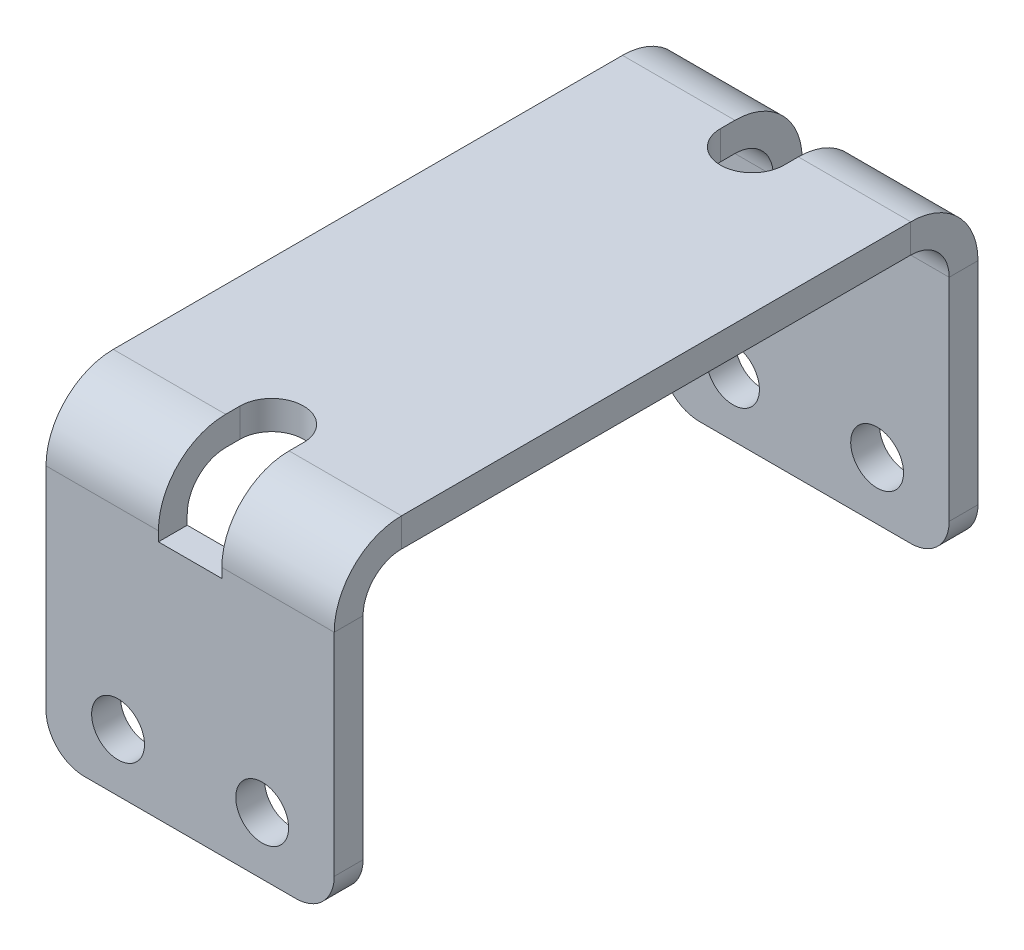
SolidWorks part; units mm, degrees
note: The reader was unsure of these and kept them because the rebuilt part matched: bend radius of "Zgięcie bazowe1", "Zgięcie bazowe2".
material "6063-T1"
ref_plane "Płaszczyzna przednia" through (0, 0, 0) normal (0, 0, 1) x (1, 0, 0)
ref_plane "Płaszczyzna górna" through (0, 0, 0) normal (0, 1, 0) x (1, 0, 0)
ref_plane "Płaszczyzna prawa" through (0, 0, 0) normal (1, 0, 0) x (0, 0, -1)
sketch "Szkic1" plane through (0, 0, 0) normal (1, 0, 0) x (0, 0, -1)
  line L0 (-30.5, 0) -> (30.5, 0)
  line L1 (30.5, 0) -> (30.5, -30)
  line L2 (-30.5, 0) -> (-30.5, -30)
  dimension "D1" = 61
  dimension "D2" = 30
base flange "Odgięcie bazowe1" sketch "Szkic1" end condition mid plane depth 30 reverse direction yes thickness 3 reverse thickness direction no bend radius 4
bend "Zgięcie bazowe1" bend radius 4 bend angle 90 parameters "D5"=1
bend "Zgięcie bazowe2" bend radius 4 bend angle 90 parameters "D5"=2
hole_wizard "Otwór pod śrubę M51" positions "Szkic6" profile "Szkic7" hole size "M5" standard "ISO" end condition through all
sketch "Szkic6" plane through (0, 0, 33.5) normal (0, 0, 1) x (1, 0, 0)
  line L0 (0, 0) -> (0, 50000) construction
  line L1 (-15, -30) -> (15, -30) construction
  point P0 (-7.5, -24)
  point P8 (7.5, -24)
  dimension "D1" = 15
  dimension "D2" = 6
sketch "Szkic7" plane through (-7.5, -24, 33.5) normal (1, 0, 0) x (0, -1, 0)
  line L0 (0, 0) -> (0, 67)
  line L1 (0, 67) -> (2.75, 67)
  line L2 (2.75, 67) -> (2.75, 0)
  line L5 (2.75, 0) -> (0, 0)
  line L11 (0, -6.35) -> (0, 107.95) construction
  dimension "Średnica otworu na wylot" = 5.5
  dimension "Głębokość otworu na wylot" = 67
fillet "Zaokrąglenie1" radius 4 4 edges at (-15, -30, -32) (15, -30, -32) (15, -30, 32) (-15, -30, 32)
hole_wizard "Otwór pod śrubę M61" positions "Szkic8" profile "Szkic9" hole size "M6" standard "ISO" end condition through all
sketch "Szkic8" plane through (0, 3, 0) normal (0, 1, 0) x (1, 0, 0)
  line L0 (0, 0) -> (50000, 0) construction
  point P0 (0, 25)
  point P8 (0, -25)
  dimension "D1" = 50
sketch "Szkic9" plane through (0, 3, -25) normal (1, 0, 0) x (0, 0, 1)
  line L0 (0, 0) -> (0, 33)
  line L1 (0, 33) -> (3.3, 33)
  line L2 (3.3, 33) -> (3.3, 0)
  line L5 (3.3, 0) -> (0, 0)
  line L11 (0, -6.35) -> (0, 107.95) construction
  dimension "Średnica otworu na wylot" = 6.6
  dimension "Głębokość otworu na wylot" = 33
sketch "Szkic10" plane through (0, 3, 0) normal (0, 1, 0) x (1, 0, 0)
  line L0 (0, 25) -> (0, 33.5) construction
  line L1 (-3.3, 25) -> (-3.3, 33.5)
  line L2 (3.3, 25) -> (3.3, 33.5)
  line L3 (-15, 33.5) -> (15, 33.5) construction
  line L4 (0, 0) -> (50000, 0) construction
  line L5 (0, -25) -> (0, -33.5) construction
  line L6 (-3.3, -25) -> (-3.3, -33.5)
  line L7 (3.3, -25) -> (3.3, -33.5)
  arc A0 (-3.3, 25) -> (3.3, 25) centre (0, 25) ccw
  arc A1 (3.3, 33.5) -> (-3.3, 33.5) centre (0, 33.5) ccw
  arc A2 (-2.9394, 26.5) -> (2.9394, 26.5) centre (0, 25) ccw construction
  arc A3 (-3.3, -25) -> (3.3, -25) centre (0, -25) cw
  arc A4 (3.3, -33.5) -> (-3.3, -33.5) centre (0, -33.5) cw
  point P4 (0, 29.25)
  point P18 (0, -29.25)
extrude "Wytnij-wyciągnięcie2" cut sketch "Szkic10" against normal blind 8
sketch "Linie zgięcia1" [suppressed] plane through (0, 0, 0) normal (0, 1, 0) x (1, 0, 0)
sketch "Ramka-graniczna1" [suppressed] plane through (0, 0, 0) normal (0, 1, 0) x (1, 0, 0)
sheet metal parameters "Arkusz blachy21" thickness 3 parameters "D1"=4
flat pattern "Rozłożony model21" [suppressed]
sketch "Linie zgięcia2" plane through (0, 0, 0) normal (0, -1, 0) x (-1, 0, 0)
  line L0 (-15, 33.4257) -> (15, 33.4257) construction
  line L1 (15, -33.4257) -> (-15, -33.4257) construction
  line L2 (-15, 33.4257) -> (15, 33.4257) construction
  line L3 (15, -33.4257) -> (-15, -33.4257) construction
sketch3d "Ramka-graniczna2" [suppressed]
  line L0 (0, 96.8514, 0) -> (0, -30.8514, 0) construction
  line L1 (-30, 96.8514, 0) -> (-30, -30.8514, 0) construction
  line L2 (0, 96.8514, 0) -> (-30, 96.8514, 0) construction
  line L3 (0, -30.8514, 0) -> (-30, -30.8514, 0) construction
bend of the flat pattern "Rozłożone-<Zgięcie bazowe1>1"
bend of the flat pattern "Rozłożone-<Zgięcie bazowe2>1"
sheet metal parameters "Arkusz blachy22" thickness 3 parameters "D1"=4
flat pattern "Rozłożony model21"
sketch "Linie zgięcia2" plane through (0, 0, 0) normal (0, -1, 0) x (-1, 0, 0)
  line L0 (-15, 33.4257) -> (15, 33.4257) construction
  line L1 (15, -33.4257) -> (-15, -33.4257) construction
  line L2 (-15, 33.4257) -> (15, 33.4257) construction
  line L3 (15, -33.4257) -> (-15, -33.4257) construction
sketch3d "Ramka-graniczna2" [suppressed]
  line L0 (0, 96.8514, 0) -> (0, -30.8514, 0) construction
  line L1 (-30, 96.8514, 0) -> (-30, -30.8514, 0) construction
  line L2 (0, 96.8514, 0) -> (-30, 96.8514, 0) construction
  line L3 (0, -30.8514, 0) -> (-30, -30.8514, 0) construction
bend of the flat pattern "Rozłożone-<Zgięcie bazowe1>1"
bend of the flat pattern "Rozłożone-<Zgięcie bazowe2>1"
sheet metal parameters "Arkusz blachy23" thickness 3 parameters "D1"=4
flat pattern "Rozłożony model21"
sketch "Linie zgięcia2" plane through (0, 0, 0) normal (0, -1, 0) x (-1, 0, 0)
  line L0 (-15, 33.4257) -> (15, 33.4257) construction
  line L1 (15, -33.4257) -> (-15, -33.4257) construction
  line L2 (-15, 33.4257) -> (15, 33.4257) construction
  line L3 (15, -33.4257) -> (-15, -33.4257) construction
sketch3d "Ramka-graniczna2" [suppressed]
  line L0 (0, 96.8514, 0) -> (0, -30.8514, 0) construction
  line L1 (-30, 96.8514, 0) -> (-30, -30.8514, 0) construction
  line L2 (0, 96.8514, 0) -> (-30, 96.8514, 0) construction
  line L3 (0, -30.8514, 0) -> (-30, -30.8514, 0) construction
bend of the flat pattern "Rozłożone-<Zgięcie bazowe1>1"
bend of the flat pattern "Rozłożone-<Zgięcie bazowe2>1"
sheet metal parameters "Arkusz blachy24" thickness 3 parameters "D1"=4
flat pattern "Rozłożony model21"
sketch "Linie zgięcia2" plane through (0, 0, 0) normal (0, -1, 0) x (-1, 0, 0)
  line L0 (-15, 30.9257) -> (-3.3, 30.9257) construction
  line L1 (15, -30.9257) -> (3.3, -30.9257) construction
  line L2 (-15, 30.9257) -> (-3.3, 30.9257) construction
  line L3 (15, -30.9257) -> (3.3, -30.9257) construction
  line L4 (3.3, 30.9257) -> (15, 30.9257) construction
  line L5 (-3.3, -30.9257) -> (-15, -30.9257) construction
sketch3d "Ramka-graniczna2" [suppressed]
  line L0 (-30.0001, 91.8514, 0) -> (-30, -30.8514, 0) construction
  line L1 (-0.0001, 91.8514, 0) -> (0, -30.8514, 0) construction
  line L2 (-30.0001, 91.8514, 0) -> (-0.0001, 91.8514, 0) construction
  line L3 (-30, -30.8514, 0) -> (0, -30.8514, 0) construction
bend of the flat pattern "Rozłożone-<Zgięcie bazowe1>1"
bend of the flat pattern "Rozłożone-<Zgięcie bazowe2>1"
